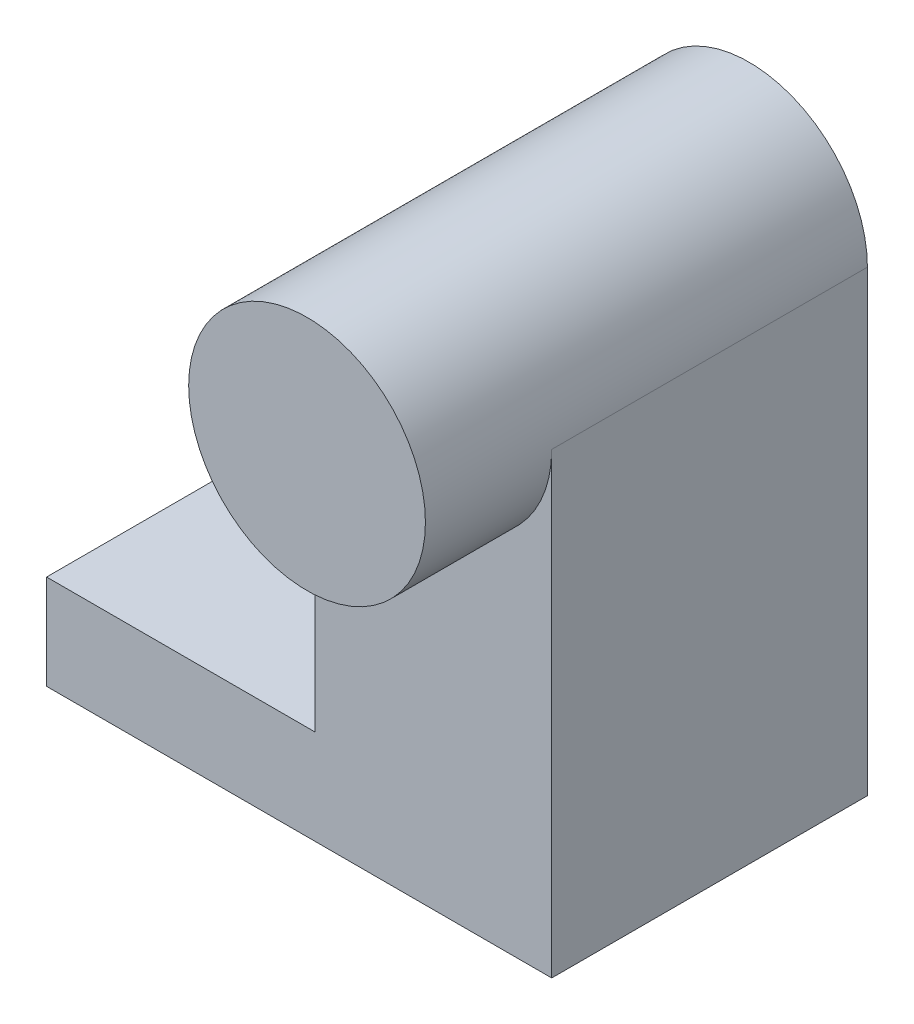
SolidWorks part; units mm, degrees
ref_plane "Front Plane" through (0, 0, 0) normal (0, 0, 1) x (1, 0, 0)
ref_plane "Top Plane" through (0, 0, 0) normal (0, 1, 0) x (1, 0, 0)
ref_plane "Right Plane" through (0, 0, 0) normal (1, 0, 0) x (0, 0, -1)
sketch "Sketch1" plane through (0, 0, 0) normal (0, 0, 1) x (1, 0, 0)
  line L0 (-7.5, 0) -> (-7.5, -7.5) construction
  line L1 (7.5, -7.5) -> (7.5, -23) construction
  line L2 (7.5, -7.5) -> (7.5, 0) construction
  line L8 (7.5, -23) -> (7.5, -29) construction
  line L10 (7.5, 0) -> (7.5, -29)
  line L11 (7.5, -29) -> (-24.5, -29)
  line L12 (-24.5, -29) -> (-24.5, -23)
  line L13 (-24.5, -23) -> (-7.5, -23)
  line L14 (-7.5, -23) -> (-7.5, 0)
  arc A0 (7.5, 0) -> (-7.5, 0) centre (0, 0) ccw construction
  arc A3 (7.5, 0) -> (-7.5, 0) centre (0, 0) ccw
  point P1 (0, 0)
  point P4 (0, 0)
  point P9 (0, 0)
  point P10 (0, 0)
  point P11 (-7.5, -8)
  point P13 (0, 0)
  point P14 (-7.5, -23)
  point P18 (0, 0)
  point P19 (0, 0)
  point P20 (0, 0)
  point P21 (0, 0)
  point P22 (0, 0)
  point P23 (0, 0)
  point P24 (0, 0)
  dimension "D1" = 15
  dimension "D2" = 6
  dimension "D3" = 17
  dimension "D4" = 7.5
  dimension "D5" = 29
extrude "Boss-Extrude1" add sketch "Sketch1" along normal blind 20
sketch "Sketch3" plane through (0, 0, 20) normal (0, 0, 1) x (1, 0, 0)
  circle A0 centre (0, 0) radius 7.5
  dimension "D1" = 15
extrude "Boss-Extrude3" add sketch "Sketch3" along normal blind 8
sketch "Sketch9" plane through (0, 0, 20) normal (0, 0, 1) x (1, 0, 0)
  line L0 (-7.5, 0) -> (-24.5, -23)
